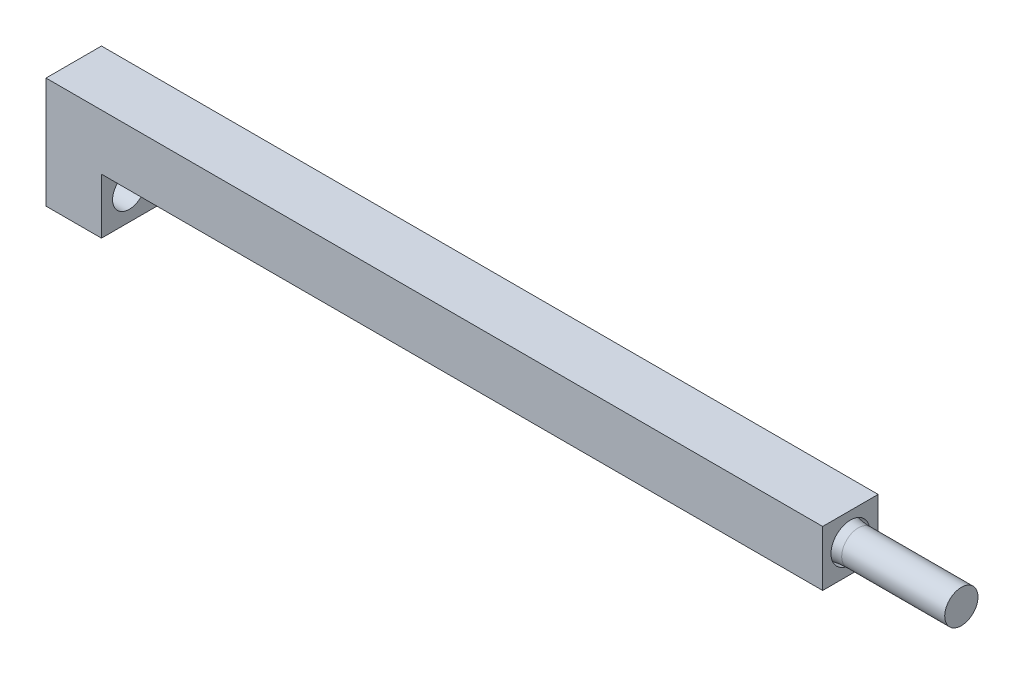
SolidWorks part; units mm, degrees
ref_plane "Front Plane" through (0, 0, 0) normal (0, 0, 1) x (1, 0, 0)
ref_plane "Top Plane" through (0, 0, 0) normal (0, 1, 0) x (1, 0, 0)
ref_plane "Right Plane" through (0, 0, 0) normal (1, 0, 0) x (0, 0, -1)
sketch "Sketch1" plane through (0, 0, 0) normal (0, 0, 1) x (1, 0, 0)
  line L1 (-140, 10) -> (0, 10)
  line L2 (-140, 10) -> (-140, -10)
  line L3 (-140, -10) -> (-130, -10)
  line L5 (-130, 0) -> (-130, -10)
  line L6 (0, 10) -> (0, -10) construction
  line L10 (0, 10) -> (0, 0)
  line L11 (-130, 0) -> (0, 0)
  point P0 (0, 0)
  point P13 (0, 0)
  dimension "D1" = 10
  dimension "D2" = 20
  dimension "D3" = 140
extrude "Boss-Extrude1" add sketch "Sketch1" along normal blind 10
sketch "Sketch4" plane through (0, 0, 0) normal (1, 0, 0) x (0, 0, -1)
  line L0 (-5, 10) -> (-5, -10) construction
  line L1 (-10, 10) -> (0, 10) construction
  line L2 (-10, -10) -> (0, -10) construction
  line L3 (-13.6296, 5) -> (2.2432, 5) construction
  line L4 (-16.8551, -5) -> (3.6579, -5) construction
  circle A0 centre (-5, 5) radius 3
  circle A1 centre (-5, -5) radius 3
  dimension "D3" = 6
  dimension "D4" = 6
  dimension "D1" = 5
  dimension "D2" = 10
extrude "Cut-Extrude2" cut sketch "Sketch4" against normal blind 150 contours A1
extrude "Boss-Extrude3" add sketch "Sketch4<5>" along normal blind 20 contours A0
sketch "Sketch4<5>" plane through (0, 0, 0) normal (1, 0, 0) x (0, 0, -1) same geometry as "Sketch4"
sketch "Sketch5" plane through (0, 0, 0) normal (1, 0, 0) x (0, 0, -1)
  circle A0 centre (-5, 5) radius 3.5
  circle A1 centre (-5, 5) radius 3 construction
  circle A2 centre (-5, 5) radius 3
  dimension "D1" = 7
extrude "Cut-Extrude4" cut sketch "Sketch5" against normal blind 2
fillet "Fillet2" radius 12 1 edges at (-2, 8, 5)
